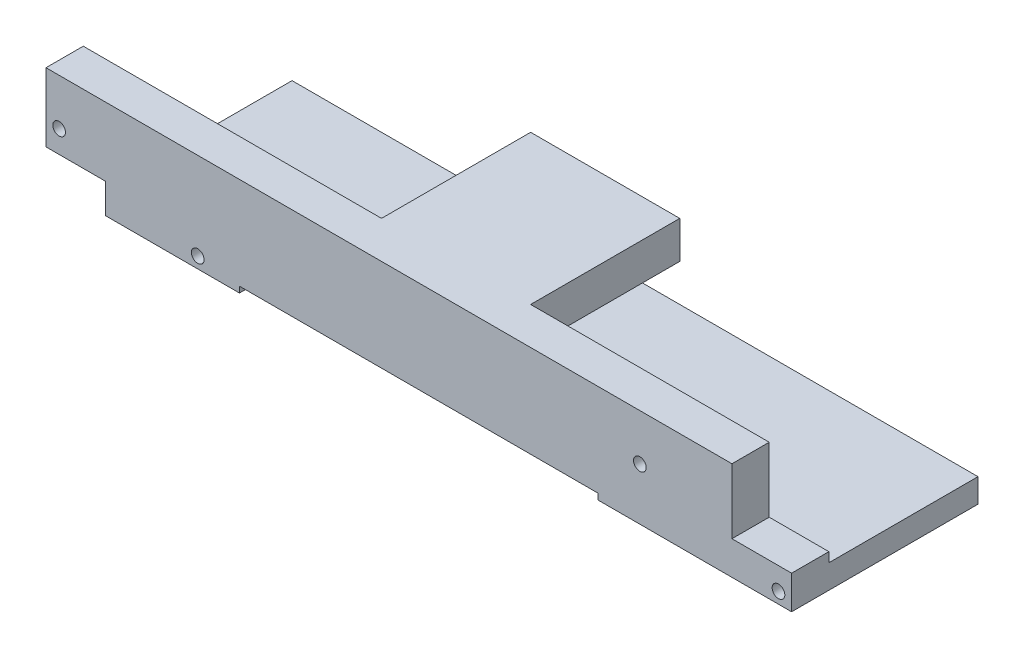
SolidWorks part; units mm, degrees
ref_plane "Front Plane" through (0, 0, 0) normal (0, 0, 1) x (1, 0, 0)
ref_plane "Top Plane" through (0, 0, 0) normal (0, 1, 0) x (1, 0, 0)
ref_plane "Right Plane" through (0, 0, 0) normal (1, 0, 0) x (0, 0, -1)
sketch "Sketch1" plane through (0, 0, 0) normal (0, 1, 0) x (1, 0, 0)
  line L1 (-63.5, -15.875) -> (63.5, -15.875)
  line L2 (-63.5, -15.875) -> (-63.5, 15.875)
  line L3 (-63.5, 15.875) -> (63.5, 15.875)
  line L4 (63.5, -15.875) -> (63.5, 15.875)
  line L5 (-63.5, -15.875) -> (63.5, 15.875) construction
  line L6 (-63.5, 15.875) -> (63.5, -15.875) construction
  point P0 (0, 0)
  dimension "D1" = 31.75
  dimension "D2" = 127
extrude "Boss-Extrude1" add sketch "Sketch1" along normal blind 16.764
sketch "Sketch2" plane through (-63.5, 0, 0) normal (-1, 0, 0) x (0, 0, 1)
  line L0 (-15.875, 16.764) -> (-15.875, 0) construction
  line L1 (-15.875, 10.414) -> (9.525, 10.414)
  line L2 (-15.875, 10.414) -> (-15.875, 4.064)
  line L3 (-15.875, 4.064) -> (9.525, 4.064)
  line L4 (9.525, 10.414) -> (9.525, 4.064)
  dimension "D1" = 6.35
  dimension "D2" = 25.4
  dimension "D3" = 4.064
extrude "Cut-Extrude1" cut sketch "Sketch2" against normal up to surface (127 mm away) up to face at (63.5, 8.382, 0)
sketch "Sketch3" plane through (-63.5, 0, 0) normal (-1, 0, 0) x (0, 0, 1)
  line L0 (9.525, 10.414) -> (-15.875, 10.414) construction
  line L1 (-15.875, 16.764) -> (9.525, 16.764)
  line L2 (-15.875, 16.764) -> (-15.875, 10.414)
  line L3 (-15.875, 10.414) -> (9.525, 10.414)
  line L4 (9.525, 16.764) -> (9.525, 10.414)
  dimension "D1" = 25.4
extrude "Cut-Extrude2" cut sketch "Sketch3" against normal blind 50.8
mirror "Mirror1" about plane through (0, 0, 0) normal (1, 0, 0) of "Cut-Extrude2"
sketch "Sketch5" plane through (0, 0, 0) normal (0, -1, 0) x (1, 0, 0)
  line L0 (-27.9908, 1.2954) -> (27.9908, 1.2954) construction
  line L1 (-63.5, 15.875) -> (63.5, 15.875) construction
  line L3 (-30.5435, 15.875) -> (30.5435, 15.875)
  line L4 (-30.5435, 15.875) -> (-30.5435, -1.2446)
  line L5 (-30.5435, -1.2446) -> (30.5435, -1.2446)
  line L6 (30.5435, 15.875) -> (30.5435, -1.2446)
  circle A0 centre (-27.9908, 1.2954) radius 1.0732
  circle A1 centre (27.9908, 1.2954) radius 1.0732
  point P0 (-27.9908, 1.2954)
  point P1 (27.9908, 1.2954)
  point P2 (0, 1.2954)
  point P12 (0, -1.2446)
  point P18 (0, -1.2446)
  line M3 (63.5, 15.875) -> (-63.5, 15.875)
  dimension "D5" = 2.1463
  dimension "D6" = 2.1463
  dimension "D1" = 2.54
  dimension "D2" = 55.9816
  dimension "D3" = 17.1196
  dimension "D4" = 61.087
extrude "Cut-Extrude3" cut sketch "Sketch5" against normal blind 1.016 contours L6 L4 L5 A0 A1 M3 | A0 | A1 region at (0, 0, 7.3571) region at (-27.9908, 0, 1.2954) region at (27.9908, 0, 1.2954)
extrude "Cut-Extrude4" cut sketch "Sketch5<3>" against normal through all contours A0 | A1 region at (-27.9908, 0, 1.2954) region at (27.9908, 0, 1.2954)
sketch "Sketch5<3>" plane through (0, 0, 0) normal (0, -1, 0) x (1, 0, 0) same geometry as "Sketch5"
sketch "Sketch6" plane through (0, 0, 15.875) normal (0, 0, 1) x (1, 0, 0)
  line L0 (-63.5, 0) -> (-30.5435, 0) construction
  line L1 (-63.5, 10.7823) -> (-36.5379, 10.7823)
  line L2 (-63.5, 10.7823) -> (-63.5, 0)
  line L3 (-63.5, 0) -> (-36.5379, 0)
  line L4 (-36.5379, 10.7823) -> (-36.5379, 0)
  line L5 (-61.2648, 8.8773) -> (-37.6555, 8.8773) construction
  line L6 (-61.2648, 8.8773) -> (-61.2648, 1.905) construction
  line L7 (-61.2648, 1.905) -> (-37.6555, 1.905) construction
  line L8 (-37.6555, 8.8773) -> (-37.6555, 1.905) construction
  line L9 (-63.5, 16.764) -> (-63.5, 0) construction
  line L10 (36.5379, 10.7823) -> (63.5, 10.7823)
  line L11 (-36.5379, 10.7823) -> (-46.6979, 10.7823)
  line L12 (-36.5379, 10.7823) -> (-36.5379, 5.7023)
  line L13 (-36.5379, 5.7023) -> (-46.6979, 5.7023)
  line L14 (-46.6979, 10.7823) -> (-46.6979, 5.7023)
  line L15 (-63.5, 0) -> (-53.34, 0)
  line L16 (-63.5, 0) -> (-63.5, 5.08)
  line L17 (-63.5, 5.08) -> (-53.34, 5.08)
  line L18 (-53.34, 0) -> (-53.34, 5.08)
  line L19 (36.5379, 10.7823) -> (36.5379, 0)
  line L20 (36.5379, 0) -> (63.5, 0)
  line L21 (63.5, 10.7823) -> (63.5, 0)
  line L22 (37.6555, 8.8773) -> (61.2648, 8.8773) construction
  line L23 (37.6555, 8.8773) -> (37.6555, 1.905) construction
  line L24 (37.6555, 1.905) -> (61.2648, 1.905) construction
  line L25 (61.2648, 8.8773) -> (61.2648, 1.905) construction
  line L26 (63.5, 10.7823) -> (53.34, 10.7823)
  line L27 (63.5, 10.7823) -> (63.5, 5.7023)
  line L28 (63.5, 5.7023) -> (53.34, 5.7023)
  line L29 (53.34, 10.7823) -> (53.34, 5.7023)
  line L30 (36.5379, 0) -> (46.6979, 0)
  line L31 (36.5379, 0) -> (36.5379, 5.08)
  line L32 (36.5379, 5.08) -> (46.6979, 5.08)
  line L33 (46.6979, 0) -> (46.6979, 5.08)
  line L34 (30.5435, 0) -> (63.5, 0) construction
  line L35 (63.5, 16.764) -> (63.5, 0) construction
  line L37 (53.34, 10.7823) -> (63.5, 10.7823)
  line L38 (53.34, 10.7823) -> (53.34, 16.764)
  line L39 (53.34, 16.764) -> (63.5, 16.764)
  line L40 (63.5, 10.7823) -> (63.5, 16.764)
  circle A0 centre (-61.2648, 8.8773) radius 1.0795
  circle A1 centre (-37.6555, 8.8773) radius 1.0795
  circle A2 centre (-37.6555, 1.905) radius 1.0795
  circle A3 centre (-61.2648, 1.905) radius 1.0795
  circle A4 centre (37.6555, 8.8773) radius 1.0795
  circle A5 centre (61.2648, 8.8773) radius 1.0795
  circle A6 centre (61.2648, 1.905) radius 1.0795
  circle A7 centre (37.6555, 1.905) radius 1.0795
  line M11 (63.5, 0) -> (63.5, 16.764)
  line M12 (63.5, 16.764) -> (-63.5, 16.764)
  line M14 (-63.5, 0) -> (-30.5435, 0)
  dimension "D7" = 2.159
  dimension "D8" = 2.159
  dimension "D9" = 2.159
  dimension "D10" = 2.159
  dimension "D21" = 2.159
  dimension "D22" = 2.159
  dimension "D23" = 2.159
  dimension "D24" = 2.159
  dimension "D1" = 26.9621
  dimension "D2" = 10.7823
  dimension "D3" = 1.1176
  dimension "D4" = 2.2352
  dimension "D5" = 1.905
  dimension "D6" = 1.905
  dimension "D11" = 10.16
  dimension "D12" = 5.08
  dimension "D13" = 10.16
  dimension "D14" = 5.08
  dimension "D15" = 26.9621
  dimension "D16" = 10.7823
  dimension "D17" = 1.1176
  dimension "D18" = 2.2352
  dimension "D19" = 1.905
  dimension "D20" = 1.905
  dimension "D25" = 10.16
  dimension "D26" = 5.08
  dimension "D27" = 10.16
  dimension "D28" = 5.08
extrude "Cut-Extrude8" cut sketch "Sketch6" against normal up to surface (31.75 mm away) contours A5 | L10 L29 L28 L21 A5 | A4 | A6 | L18 L17 L2 A3 M14 | A3 | A2 | A0 | L38 L10 M11 M12 region at (-58.2028, 2.5885, 15.875) region at (58.42, 13.7732, 15.875) region at (58.2028, 8.1938, 15.875) region at (-61.2648, 8.8773, 15.875) region at (-37.6555, 1.905, 15.875) region at (-61.2648, 1.905, 15.875) region at (37.6555, 8.8773, 15.875) region at (61.2648, 8.8773, 15.875) region at (61.2648, 1.905, 15.875) up to face at (0, 2.032, -15.875)
